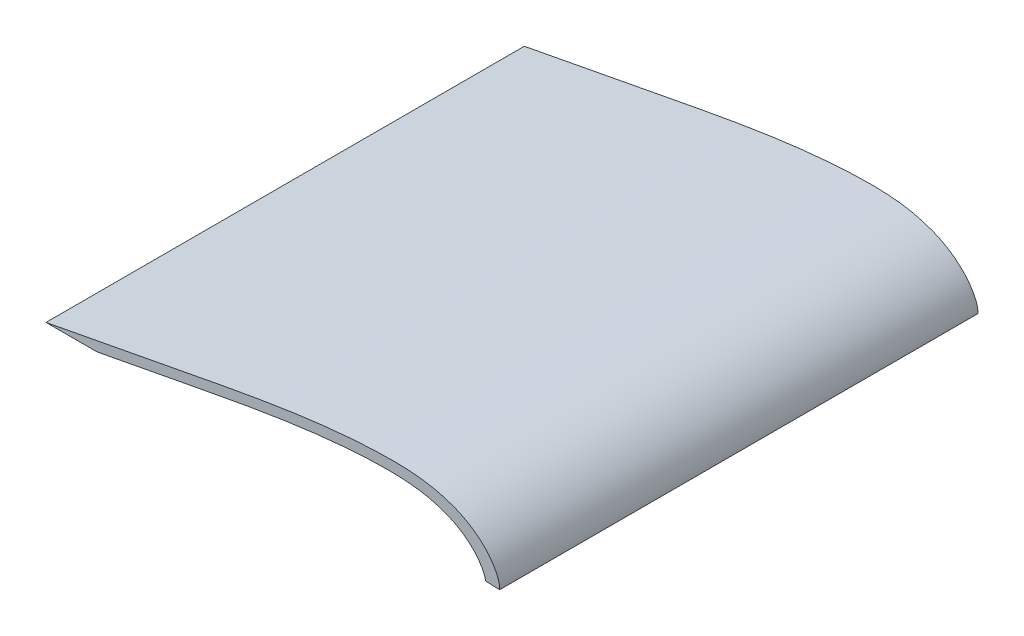
SolidWorks part; units mm, degrees
ref_plane "Front Plane" through (0, 0, 0) normal (0, 0, 1) x (1, 0, 0)
ref_plane "Top Plane" through (0, 0, 0) normal (0, 1, 0) x (1, 0, 0)
ref_plane "Right Plane" through (0, 0, 0) normal (1, 0, 0) x (0, 0, -1)
sketch "Sketch3" plane through (0, 0, 0) normal (0, 0, 1) x (1, 0, 0)
  line L0 (-35.4155, 0.9786) -> (-46.127, 0.9786)
  line L1 (45.7527, 0.1003) -> (48.7207, 0)
  line L2 (48.7207, 0) -> (-34.4545, 0) construction
  spline S0 degree 3 poles (48.7207, 0) (48.7413, 1.212) (48.0464, 2.8572) (46.8151, 4.7839) (45.4925, 6.3024) (43.8268, 7.7408) (41.4946, 9.2643) (38.1681, 10.7172) (33.7887, 11.8315) (28.7294, 12.2559) (23.717, 12.2188) (17.039, 11.8576) (8.6903, 10.9743) (-1.3041, 9.4479) (-11.2877, 7.6112) (-21.2786, 5.6967) (-34.613, 3.1689) (-44.6124, 1.2656) (-51.2793, 0) knots 0 0 0 0 0.032627 0.049883 0.064276 0.089251 0.111668 0.142584 0.191136 0.23834 0.285329 0.332382 0.426847 0.521876 0.617364 0.713023 0.808682 1 1 1 1
  spline S1 degree 3 poles (-35.4155, 0.9786) (-31.9007, 1.6464) (-28.3857, 2.3126) (-21.3563, 3.6489) (-17.8426, 4.3227) (-10.8123, 5.6541) (-7.2961, 6.3141) (-0.2462, 7.5388) (3.2897, 8.1009) (10.3826, 9.0556) (13.9397, 9.4499) (19.2948, 9.846) (21.0805, 9.9456) (24.6541, 10.0538) (26.4418, 10.0626) (29.1266, 9.9312) (30.0211, 9.8625) (31.7935, 9.6561) (32.6728, 9.5176) (34.415, 9.1542) (35.2779, 8.9305) (36.5587, 8.5235) (36.9845, 8.3756) (37.8235, 8.0564) (38.6499, 7.7134) (39.4456, 7.3119) (40.2226, 6.8751) (40.6019, 6.6392) (41.343, 6.1342) (41.7066, 5.8644) (42.4051, 5.299) (42.7404, 5.0027) (43.379, 4.3788) (43.6829, 4.0517) (44.2484, 3.3563) (44.5091, 2.9837) (44.8649, 2.4053) (44.978, 2.2096) (45.194, 1.8126) (45.2964, 1.6111) (45.4811, 1.1971) (45.5636, 0.9838) (45.6906, 0.5499) (45.7355, 0.3285) (45.7527, 0.1003) knots 0 0 0 0 0.125 0.125 0.25 0.25 0.375 0.375 0.5 0.5 0.625 0.625 0.6875 0.6875 0.75 0.75 0.78125 0.78125 0.8125 0.8125 0.84375 0.84375 0.859375 0.859375 0.875 0.890625 0.890625 0.90625 0.90625 0.921875 0.921875 0.9375 0.9375 0.953125 0.953125 0.96875 0.96875 0.976562 0.976562 0.984375 0.984375 0.992188 0.992188 1 1 1 1
  point P6 (0, 0)
  point P8 (0, 0)
extrude "Boss-Extrude1" add sketch "Sketch3" along normal mid plane 100 contours L0 S1 L1 S0 region at (-40.7712, 1.9349, 0)
sketch "Sketch4" plane through (0, 0, 0) normal (0, 1, 0) x (1, 0, 0)
  line L0 (48.7207, -50) -> (48.7207, 50) construction
  line L1 (48.7207, -50) -> (48.7207, 50)
  line L2 (48.7207, 0) -> (-13.2793, 0) construction
  circle A0 centre (-13.2793, 0) radius 4.9
  dimension "D1" = 9.8
  dimension "D2" = 62
extrude "Boss-Extrude2" add sketch "Sketch4" along normal up to surface and the other way blind 0.46 contours A0 region at (-13.2793, 0, 0) up to face at (-15.1234, 0.759, 0)
sketch "Sketch5" plane through (0, 0, 0) normal (0, 0, 1) x (1, 0, 0)
  line L1 (-8.3793, -0.46) -> (-8.3793, 6.1015) construction
  line L2 (-8.3793, -0.46) -> (-8.3793, 6.1015)
  line L3 (-18.1793, 4.2563) -> (-18.1793, -0.46) construction
  line L4 (-18.1793, 4.2563) -> (-18.1793, -0.46)
  spline S1 degree 3 poles (-525.0903, -2862.9343) (-687.8734, -106.1956) (-354.8821, -59.7534) (-21.3563, 3.6489) (-17.8426, 4.3227) (-10.8123, 5.6541) (-7.2961, 6.3141) (-0.2462, 7.5388) (3.2897, 8.1009) (10.3826, 9.0556) (13.9397, 9.4499) (19.2948, 9.846) (21.0805, 9.9456) (24.6541, 10.0538) (26.4418, 10.0626) (29.1266, 9.9312) (30.0211, 9.8625) (31.7935, 9.6561) (32.6728, 9.5176) (34.415, 9.1542) (35.2779, 8.9305) (36.5587, 8.5235) (36.9845, 8.3756) (37.8235, 8.0564) (38.6499, 7.7134) (39.4456, 7.3119) (40.2226, 6.8751) (40.6019, 6.6392) (41.343, 6.1342) (41.7066, 5.8644) (42.4051, 5.299) (42.7404, 5.0027) (43.379, 4.3788) (43.6829, 4.0517) (44.2484, 3.3563) (44.5091, 2.9837) (44.8649, 2.4053) (44.978, 2.2096) (45.194, 1.8126) (45.2964, 1.6111) (45.4811, 1.1971) (45.5636, 0.9838) (49.8278, -13.5819) (-27.1275, -47.71) (-2855.9649, -752.5254) knots -11.611785 -11.611785 -11.611785 -11.611785 0.125 0.125 0.25 0.25 0.375 0.375 0.5 0.5 0.625 0.625 0.6875 0.6875 0.75 0.75 0.78125 0.78125 0.8125 0.8125 0.84375 0.84375 0.859375 0.859375 0.875 0.890625 0.890625 0.90625 0.90625 0.921875 0.921875 0.9375 0.9375 0.953125 0.953125 0.96875 0.96875 0.976562 0.976562 0.984375 0.984375 0.992188 0.992188 1.508965 1.508965 1.508965 1.508965 only from (-35.4155, 0.9786) to (45.7527, 0.1003) construction
  spline S2 degree 3 poles (-35.4155, 0.9786) (-31.9007, 1.6464) (-28.3857, 2.3126) (-21.3563, 3.6489) (-17.8426, 4.3227) (-10.8123, 5.6541) (-7.2961, 6.3141) (-0.2462, 7.5388) (3.2897, 8.1009) (10.3826, 9.0556) (13.9397, 9.4499) (19.2948, 9.846) (21.0805, 9.9456) (24.6541, 10.0538) (26.4418, 10.0626) (29.1266, 9.9312) (30.0211, 9.8625) (31.7935, 9.6561) (32.6728, 9.5176) (34.415, 9.1542) (35.2779, 8.9305) (36.5587, 8.5235) (36.9845, 8.3756) (37.8235, 8.0564) (38.6499, 7.7134) (39.4456, 7.3119) (40.2226, 6.8751) (40.6019, 6.6392) (41.343, 6.1342) (41.7066, 5.8644) (42.4051, 5.299) (42.7404, 5.0027) (43.379, 4.3788) (43.6829, 4.0517) (44.2484, 3.3563) (44.5091, 2.9837) (44.8649, 2.4053) (44.978, 2.2096) (45.194, 1.8126) (45.2964, 1.6111) (45.4811, 1.1971) (45.5636, 0.9838) (45.6906, 0.5499) (45.7355, 0.3285) (45.7527, 0.1003) knots 0 0 0 0 0.125 0.125 0.25 0.25 0.375 0.375 0.5 0.5 0.625 0.625 0.6875 0.6875 0.75 0.75 0.78125 0.78125 0.8125 0.8125 0.84375 0.84375 0.859375 0.859375 0.875 0.890625 0.890625 0.90625 0.90625 0.921875 0.921875 0.9375 0.9375 0.953125 0.953125 0.96875 0.96875 0.976562 0.976562 0.984375 0.984375 0.992188 0.992188 1 1 1 1
  point P0 (-18.1793, 4.2563)
  point P1 (-18.1793, -0.46)
  point P5 (-8.3793, -0.46)
  point P8 (0, 0)
  dimension "D1" = 6.5615
  dimension "D2" = 4.7163
